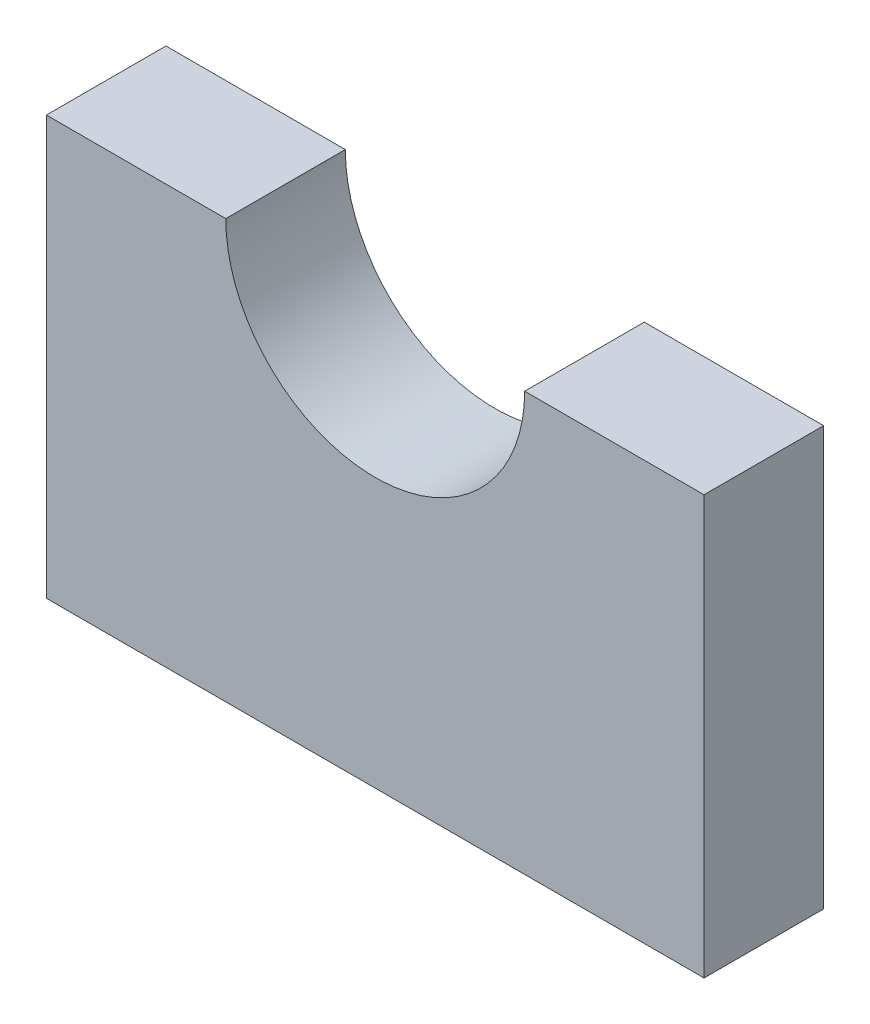
SolidWorks part; units mm, degrees
ref_plane "Front" through (0, 0, 0) normal (0, 0, 1) x (1, 0, 0)
ref_plane "Top" through (0, 0, 0) normal (0, 1, 0) x (1, 0, 0)
ref_plane "Right" through (0, 0, 0) normal (1, 0, 0) x (0, 0, -1)
sketch "Sketch1" plane through (0, 0, 0) normal (0, 1, 0) x (1, 0, 0)
  line L1 (34.925, -6.35) -> (-34.925, -6.35)
  line L2 (34.925, -6.35) -> (34.925, 6.35)
  line L3 (34.925, 6.35) -> (-34.925, 6.35)
  line L4 (-34.925, -6.35) -> (-34.925, 6.35)
  line L5 (34.925, -6.35) -> (-34.925, 6.35) construction
  line L6 (34.925, 6.35) -> (-34.925, -6.35) construction
  point P0 (0, 0)
  dimension "D1" = 12.7
  dimension "D2" = 69.85
extrude "Boss-Extrude1" add sketch "Sketch1" along normal blind 44.45
sketch "Sketch3" plane through (0, 0, -6.35) normal (0, 0, -1) x (-1, 0, 0)
  line L0 (-34.925, 44.45) -> (34.925, 44.45) construction
  circle A0 centre (0, 44.45) radius 15.875
  dimension "D1" = 31.75
extrude "Cut-Extrude3" cut sketch "Sketch3" against normal blind 25.4
sketch "Sketch4" plane through (0, 0, 0) normal (0, -1, 0) x (-1, 0, 0)
  line L0 (-55, 0) -> (55, 0) construction
  line L1 (0, 55) -> (0, -55) construction
  circle A0 centre (25.4, 0) radius 1.27
  circle A1 centre (-25.4, 0) radius 1.27
  dimension "D3" = 2.54
  dimension "D4" = 2.54
  dimension "D1" = 25.4
  dimension "D2" = 25.4
extrude "Cut-Extrude4" cut sketch "Sketch4" against normal blind 5.08
